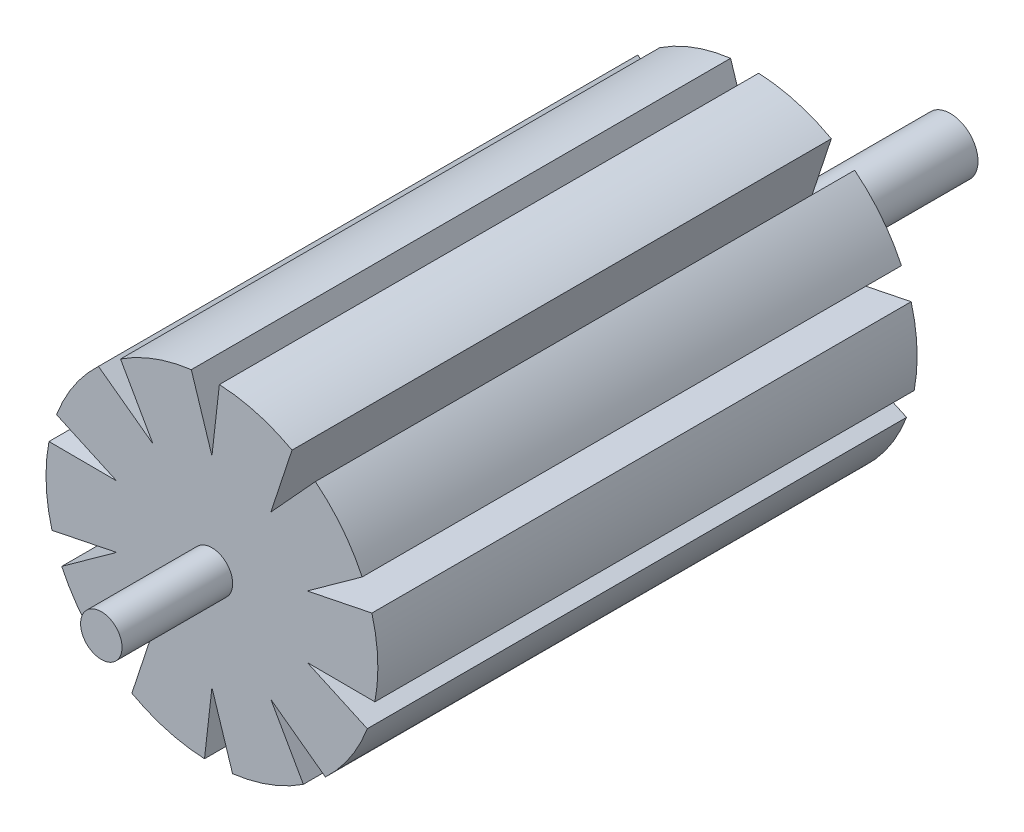
SolidWorks part; units mm, degrees
material "Ductile Iron"
ref_plane "Front Plane" through (0, 0, 0) normal (0, 0, 1) x (1, 0, 0)
ref_plane "Top Plane" through (0, 0, 0) normal (0, 1, 0) x (1, 0, 0)
ref_plane "Right Plane" through (0, 0, 0) normal (1, 0, 0) x (0, 0, -1)
sketch "Sketch1" plane through (0, 0, 0) normal (0, 0, 1) x (1, 0, 0)
  line L0 (0, 6) -> (0, -6) construction
  line L1 (0, 3.6247) -> (0.8943, 11.5091)
  line L2 (0, 3.6247) -> (-2.4705, 11.3366)
  line L3 (-2.4705, 11.3366) -> (0.8943, 11.5091)
  line L4 (4.6648, 10.6236) -> (7.4884, 8.7854)
  line L5 (2.1306, 2.9325) -> (7.4884, 8.7854)
  line L6 (2.1306, 2.9325) -> (4.6648, 10.6236)
  line L7 (10.0183, 5.8528) -> (11.2221, 2.706)
  line L8 (3.4473, 1.1201) -> (11.2221, 2.706)
  line L9 (3.4473, 1.1201) -> (10.0183, 5.8528)
  line L10 (11.5452, -1.1536) -> (10.6694, -4.407)
  line L11 (3.4473, -1.1201) -> (10.6694, -4.407)
  line L12 (3.4473, -1.1201) -> (11.5452, -1.1536)
  line L13 (8.6621, -7.7194) -> (6.0414, -9.8367)
  line L14 (2.1306, -2.9325) -> (6.0414, -9.8367)
  line L15 (2.1306, -2.9325) -> (8.6621, -7.7194)
  line L16 (2.4705, -11.3366) -> (-0.8943, -11.5091)
  line L17 (0, -3.6247) -> (-0.8943, -11.5091)
  line L18 (0, -3.6247) -> (2.4705, -11.3366)
  line L19 (-4.6648, -10.6236) -> (-7.4884, -8.7854)
  line L20 (-2.1306, -2.9325) -> (-7.4884, -8.7854)
  line L21 (-2.1306, -2.9325) -> (-4.6648, -10.6236)
  line L22 (-10.0183, -5.8528) -> (-11.2221, -2.706)
  line L23 (-3.4473, -1.1201) -> (-11.2221, -2.706)
  line L24 (-3.4473, -1.1201) -> (-10.0183, -5.8528)
  line L25 (-11.5452, 1.1536) -> (-10.6694, 4.407)
  line L26 (-3.4473, 1.1201) -> (-10.6694, 4.407)
  line L27 (-3.4473, 1.1201) -> (-11.5452, 1.1536)
  line L28 (-8.6621, 7.7194) -> (-6.0414, 9.8367)
  line L29 (-2.1306, 2.9325) -> (-6.0414, 9.8367)
  line L30 (-2.1306, 2.9325) -> (-8.6621, 7.7194)
  circle A0 centre (0, 0) radius 6
  circle A1 centre (0, 0) radius 1
  point P10 (0, 0)
  point P11 (0, 0)
  point P38 (0, 0)
  point P39 (0, 0)
  point P40 (0, 0)
  point P41 (0, 0)
  dimension "D1" = 10
extrude "Boss-Extrude1" add sketch "Sketch1" along normal blind 19.5 contours A0
extrude "Boss-Extrude2" add sketch "Sketch1<3>" against normal blind 7.2 contours A1
sketch "Sketch1<3>" plane through (0, 0, 0) normal (0, 0, 1) x (1, 0, 0) same geometry as "Sketch1"
extrude "Cut-Extrude4" cut sketch "Sketch1<6>" along normal blind 55 contours L8 L7 L9 | L5 L4 L6 | L2 L3 L1 | L23 L22 L24 | L20 L19 L21 | L17 L16 L18 | L14 L13 L15 | L11 L10 L12 | L29 L28 L30 | L26 L25 L27
sketch "Sketch1<6>" plane through (0, 0, 0) normal (0, 0, 1) x (1, 0, 0) same geometry as "Sketch1"
sketch "Sketch2" plane through (0, 0, 19.5) normal (0, 0, 1) x (1, 0, 0)
  circle A0 centre (0, 0) radius 0.75
extrude "Boss-Extrude3" add sketch "Sketch2" along normal blind 4 contours A0
